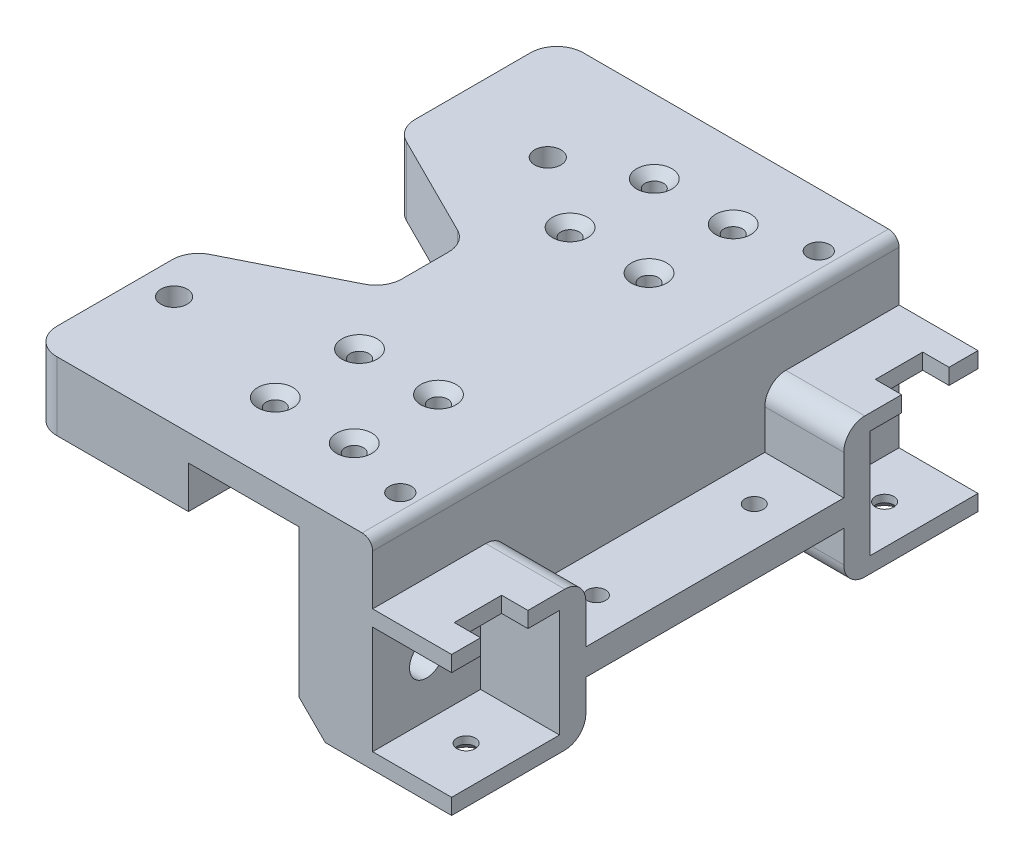
SolidWorks part; units mm, degrees
ref_plane "Front Plane" through (0, 0, 0) normal (0, 0, 1) x (1, 0, 0)
ref_plane "Top Plane" through (0, 0, 0) normal (0, 1, 0) x (1, 0, 0)
ref_plane "Right Plane" through (0, 0, 0) normal (1, 0, 0) x (0, 0, -1)
sketch "Sketch1" plane through (0, 0, 0) normal (0, 1, 0) x (1, 0, 0)
  line L0 (0, 50) -> (0, -50) construction
  line L1 (-10, 50) -> (10, 50)
  line L2 (-10, 50) -> (-10, -50)
  line L3 (-10, -50) -> (10, -50)
  line L4 (10, 50) -> (10, -50) construction
  line L5 (-10, 50) -> (10, -50) construction
  line L6 (-10, -50) -> (10, 50) construction
  line L7 (-7.5, 36) -> (7.5, 36) construction
  line L8 (-7.5, 36) -> (7.5, 20) construction
  line L9 (-10, 0) -> (10, 0) construction
  line L10 (-7.5, -36) -> (7.5, -20) construction
  line L11 (-7.5, -36) -> (7.5, -36) construction
  line L12 (-7.5, 20) -> (7.5, 20) construction
  line L13 (10, 50) -> (11, 50)
  line L14 (11, 50) -> (11, -50)
  line L15 (11, -50) -> (10, -50)
  circle A0 centre (-7.5, 36) radius 1.75
  circle A1 centre (7.5, 36) radius 1.75
  circle A2 centre (-7.5, 20) radius 1.75
  circle A3 centre (7.5, 20) radius 1.75
  circle A4 centre (7.5, -20) radius 1.75
  circle A5 centre (-7.5, -20) radius 1.75
  circle A6 centre (7.5, -36) radius 1.75
  circle A7 centre (-7.5, -36) radius 1.75
  point P0 (0, 0)
  point P16 (0, 36)
  dimension "D2" = 3.5
  dimension "D1" = 20
  dimension "D3" = 15
  dimension "D4" = 16
  dimension "D5" = 100
  dimension "D6" = 20
  dimension "D7" = 1
extrude "Boss-Extrude1" add sketch "Sketch1" along normal blind 5
sketch "Sketch2" plane through (11, 0, 0) normal (1, 0, 0) x (0, 0, -1)
  line L1 (-50, 5) -> (50, 5)
  line L2 (-50, 5) -> (-50, -33)
  line L3 (-50, -33) -> (50, -33)
  line L5 (50, 5) -> (50, -33)
  line L6 (50, 5) -> (50, 0) construction
  line L7 (-50, 5) -> (-50, 0) construction
  line L8 (-50, 5) -> (50, 5) construction
  dimension "D1" = 38
extrude "Boss-Extrude2" add sketch "Sketch2" along normal blind 14
sketch "Sketch3" plane through (25, 0, 0) normal (1, 0, 0) x (0, 0, -1)
  line L0 (0, 5) -> (0, -33) construction
  line L1 (-25, -18) -> (25, -18)
  line L2 (-25, -18) -> (-25, -23)
  line L3 (-25, -23) -> (25, -23)
  line L4 (25, -18) -> (25, -23)
  line L5 (50, 5) -> (-50, 5) construction
  line L6 (-50, -33) -> (50, -33) construction
  point P10 (0, -18)
  dimension "D1" = 5
  dimension "D2" = 50
  dimension "D3" = 10
extrude "Boss-Extrude3" add sketch "Sketch3" along normal blind 15
sketch "Sketch4" plane through (0, -18, 0) normal (0, 1, 0) x (1, 0, 0)
  line L0 (25, 0) -> (40, 0) construction
  line L1 (25, 25) -> (25, -25) construction
  line L2 (40, 25) -> (40, -25) construction
  line L3 (32.5, -15) -> (32.5, 15) construction
  circle A0 centre (32.5, 15) radius 1.75
  circle A1 centre (32.5, -15) radius 1.75
  point P8 (32.5, 0)
  dimension "D1" = 30
  dimension "D2" = 3.5
extrude "Cut-Extrude1" cut sketch "Sketch4" against normal through all
sketch "Sketch8" plane through (25, 0, 0) normal (1, 0, 0) x (0, 0, -1)
  line L0 (-50, 5) -> (-50, -33) construction
  line L1 (-50, -6.5) -> (-24.5, -6.5)
  line L2 (-50, -6.5) -> (-50, -9.5)
  line L3 (-50, -33) -> (-24.5, -33)
  line L4 (-24.5, -6.5) -> (-24.5, -33)
  line L5 (-50, -30) -> (-50, -33)
  line L6 (-50, -30) -> (-29.5, -30)
  line L8 (-50, -9.5) -> (-29.5, -9.5)
  line L9 (-29.5, -30) -> (-29.5, -9.5)
  line L10 (0, 20.9) -> (0, -20.9) construction
  line L11 (29.5, -30) -> (29.5, -9.5)
  line L12 (50, -9.5) -> (29.5, -9.5)
  line L13 (50, -30) -> (29.5, -30)
  line L14 (50, -30) -> (50, -33)
  line L15 (24.5, -6.5) -> (24.5, -33)
  line L16 (50, -33) -> (24.5, -33)
  line L17 (50, -6.5) -> (50, -9.5)
  line L18 (50, -6.5) -> (24.5, -6.5)
  line L19 (-50, -33) -> (50, -33) construction
  dimension "D1" = 3
  dimension "D2" = 5
  dimension "D3" = 3
  dimension "D4" = 20.5
  dimension "D5" = 20.5
extrude "Boss-Extrude6" add sketch "Sketch8" along normal blind 15
sketch "Sketch9" plane through (25, 0, 0) normal (1, 0, 0) x (0, 0, -1)
  line L0 (-50, -9.5) -> (-29.5, -30) construction
  line L1 (50, -9.5) -> (29.5, -30) construction
  circle A0 centre (-39.75, -19.75) radius 3.25
  circle A1 centre (39.75, -19.75) radius 3.25
  dimension "D1" = 6.5
extrude "Cut-Extrude3" cut sketch "Sketch9" against normal through all
sketch "Sketch10" plane through (11, 0, 0) normal (-1, 0, 0) x (0, 0, 1)
  circle A0 centre (-39.75, -19.75) radius 5.25
  circle A1 centre (39.75, -19.75) radius 5.25
  dimension "D1" = 10.5
extrude "Cut-Extrude4" cut sketch "Sketch10" against normal offset from surface (9 mm away) 5 up to face at (25, -19.75, 36.5)
sketch "Sketch11" plane through (0, -6.5, 0) normal (0, 1, 0) x (1, 0, 0)
  line L0 (40, -24.5) -> (40, -50) construction
  line L1 (40, -35.5) -> (35, -35.5)
  line L2 (40, -35.5) -> (40, -44.5)
  line L3 (40, -44.5) -> (35, -44.5)
  line L4 (35, -35.5) -> (35, -44.5)
  line L5 (35, -40) -> (40, -40) construction
  line L6 (40, -50) -> (25, -50) construction
  line L7 (-10, 0) -> (40, 0) construction
  line L8 (-10, 50) -> (-10, -50) construction
  line L9 (40, 24.5) -> (40, -24.5) construction
  line L10 (40, -35.5) -> (35, -35.5)
  line L11 (40, -44.5) -> (35, -44.5)
  line L12 (35, 40) -> (40, 40) construction
  line L13 (40, 44.5) -> (35, 44.5)
  line L14 (40, 35.5) -> (35, 35.5)
  line L15 (35, 35.5) -> (35, 44.5)
  line L16 (40, 44.5) -> (35, 44.5)
  line L17 (40, 35.5) -> (40, 44.5)
  line L18 (40, 35.5) -> (35, 35.5)
  line M7 (40, -50) -> (40, -24.5)
  dimension "D1" = 9
  dimension "D2" = 10
  dimension "D3" = 5
extrude "Cut-Extrude5" cut sketch "Sketch11" against normal up to next contours L1 L4 L3 M7 | L14 L17 L13 L15 region at (37.5, -6.5, 40) region at (37.5, -6.5, -40)
sketch "Sketch12" plane through (0, -30, 0) normal (0, 1, 0) x (1, 0, 0)
  line L0 (40, -39.75) -> (25, -39.75) construction
  line L1 (40, -29.5) -> (40, -50) construction
  line L2 (25, -24.5) -> (25, -50) construction
  line L3 (-20.9, 0) -> (20.9, 0) construction
  circle A0 centre (32.5, -39.75) radius 1.75
  circle A2 centre (32.5, 39.75) radius 1.75
  dimension "D1" = 3.5
extrude "Cut-Extrude6" cut sketch "Sketch12" against normal through all
sketch "Sketch13" plane through (-10, 0, 0) normal (-1, 0, 0) x (0, 0, 1)
  line L1 (-50, 5) -> (50, 5)
  line L2 (-50, 5) -> (-50, -8)
  line L3 (-50, -8) -> (50, -8)
  line L4 (50, 5) -> (50, -8)
  dimension "D1" = 13
extrude "Boss-Extrude7" add sketch "Sketch13" along normal blind 30
sketch "Sketch14" plane through (0, 5, 0) normal (0, 1, 0) x (1, 0, 0)
  line L0 (-40, -50) -> (25, -50) construction
  line L1 (-10.5, -50) -> (10.5, -50) construction
  line L2 (-10.5, -50) -> (-10.5, 50) construction
  line L3 (-10.5, 50) -> (10.5, 50) construction
  line L4 (10.5, -50) -> (10.5, 50) construction
  line L5 (25, 50) -> (-40, 50) construction
  line L6 (-27.23, 29.42) -> (-27.23, -29) construction
  line L12 (-33.73, -35.5) -> (40, -35.5) construction
  line L18 (-21.15, 35.5) -> (40, 35.5) construction
  circle A0 centre (-21.15, 29.42) radius 2.5
  circle A1 centre (-33.73, -29) radius 2.5
  circle A2 centre (-33.73, -29) radius 6.5 construction
  circle A3 centre (-21.15, 29.42) radius 6.08 construction
  point P14 (0, 50)
  dimension "D1" = 5
  dimension "D2" = 5
  dimension "D4" = 21
  dimension "D5" = 13
  dimension "D6" = 12.16
  dimension "D3" = 21.15
extrude "Cut-Extrude7" cut sketch "Sketch14" against normal through all
sketch "Sketch15" plane through (0, -8, 0) normal (0, -1, 0) x (1, 0, 0)
  line L0 (-40, -50) -> (-40, 50) construction
  line L1 (-29.73, 26.6906) -> (-29.73, 31.3094)
  line L2 (-29.73, 31.3094) -> (-33.73, 33.6188)
  line L3 (-33.73, 33.6188) -> (-37.73, 31.3094)
  line L4 (-37.73, 31.3094) -> (-37.73, 26.6906)
  line L5 (-37.73, 26.6906) -> (-33.73, 24.3812)
  line L6 (-33.73, 24.3812) -> (-29.73, 26.6906)
  line L7 (-25.15, -31.7294) -> (-21.15, -34.0388)
  line L8 (-21.15, -34.0388) -> (-17.15, -31.7294)
  line L9 (-17.15, -31.7294) -> (-17.15, -27.1106)
  line L10 (-17.15, -27.1106) -> (-21.15, -24.8012)
  line L11 (-21.15, -24.8012) -> (-25.15, -27.1106)
  line L12 (-25.15, -27.1106) -> (-25.15, -31.7294)
  circle A0 centre (-33.73, 29) radius 4 construction
  circle A1 centre (-21.15, -29.42) radius 4 construction
  dimension "D1" = 8
extrude "Cut-Extrude8" cut sketch "Sketch15" against normal blind 4
sketch "Sketch16" plane through (0, 5, 0) normal (0, 1, 0) x (1, 0, 0)
  line L0 (20, 39.75) -> (40, 39.75) construction
  line L1 (40, 50) -> (40, 29.5) construction
  line L2 (20, -39.75) -> (40, -39.75) construction
  line L3 (40, -29.5) -> (40, -50) construction
  circle A0 centre (20, 39.75) radius 2.1
  circle A1 centre (20, -39.75) radius 2.1
  dimension "D1" = 4.2
  dimension "D2" = 4.2
  dimension "D3" = 20
extrude "Cut-Extrude9" cut sketch "Sketch16" against normal blind 4
chamfer "Chamfer1" distance 1.6 angle 45 8 edges at (-7.5, 5, -34.25) (7.5, 5, -34.25) (-7.5, 5, -18.25) (7.5, 5, -18.25) (-7.5, 5, 18.25) (7.5, 5, 18.25) (-7.5, 5, 34.25) (7.5, 5, 34.25)
sketch "Sketch17" plane through (0, 5, 0) normal (0, 1, 0) x (1, 0, 0)
  line L0 (-40, 20) -> (-15, 7.5)
  line L1 (-40, -50) -> (-40, 50) construction
  line L2 (-15, 7.5) -> (-15, -7.5)
  line L3 (-15, -7.5) -> (-40, -20)
  line L4 (-40, -20) -> (-40, 20)
  point P6 (-15, 0)
  dimension "D1" = 15
  dimension "D2" = 40
  dimension "D3" = 15
extrude "Cut-Extrude10" cut sketch "Sketch17" against normal through all
chamfer "Chamfer2" distance 1.6 angle 45 2 edges at (32.5, -33, -41.5) (32.5, -33, 41.5)
chamfer "Chamfer3" distance 5 angle 45 1 edges at (11, -33, 0)
sketch "Sketch18" plane through (0, 1, 0) normal (0, 1, 0) x (1, 0, 0)
  circle A0 centre (20, 39.75) radius 1.75
  circle A1 centre (20, -39.75) radius 1.75
  dimension "D1" = 3.5
  dimension "D2" = 3.5
extrude "Cut-Extrude11" cut sketch "Sketch18" against normal blind 4
fillet "Fillet1" radius 5 6 edges at (-40, -1.5, -50) (-40, -1.5, 50) (-40, -1.5, 20) (-15, -1.5, 7.5) (-15, -1.5, -7.5) (-40, -1.5, -20)
fillet "Fillet2" radius 2 1 edges at (25, 5, 0)
fillet "Fillet3" radius 4 4 edges at (32.5, -33, -24.5) (32.5, -6.5, -24.5) (32.5, -6.5, 24.5) (32.5, -33, 24.5)
